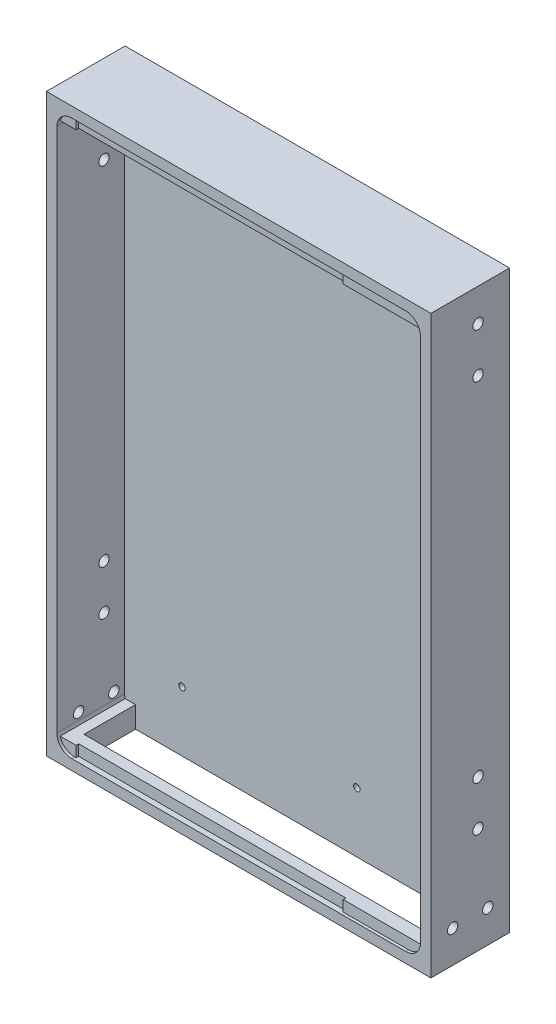
SolidWorks part; units mm, degrees
ref_plane "Front Plane" through (0, 0, 0) normal (0, 0, 1) x (1, 0, 0)
ref_plane "Top Plane" through (0, 0, 0) normal (0, 1, 0) x (1, 0, 0)
ref_plane "Right Plane" through (0, 0, 0) normal (1, 0, 0) x (0, 0, -1)
sketch "Sketch1" plane through (0, 0, 0) normal (0, 0, 1) x (1, 0, 0)
  line L1 (-88.5, -132.5) -> (88.5, -132.5)
  line L2 (-88.5, -132.5) -> (-88.5, 132.5)
  line L3 (-88.5, 132.5) -> (88.5, 132.5)
  line L4 (88.5, -132.5) -> (88.5, 132.5)
  line L5 (-88.5, -132.5) -> (88.5, 132.5) construction
  line L6 (-88.5, 132.5) -> (88.5, -132.5) construction
  circle A0 centre (-57.3, -104.9) radius 1.5 construction
  circle A1 centre (23.21, -104.9) radius 1.5 construction
  circle A2 centre (23.21, 104.9) radius 1.5 construction
  circle A3 centre (-57.3, 104.9) radius 1.5 construction
  circle A4 centre (-57.3, -104.9) radius 1.5
  circle A5 centre (23.21, -104.9) radius 1.5
  circle A6 centre (23.21, 104.9) radius 1.5
  circle A7 centre (-57.3, 104.9) radius 1.5
  point P0 (0, 0)
  dimension "D1" = 177
  dimension "D2" = 265
extrude "Boss-Extrude1" add sketch "Sketch1" along normal blind 5
sketch "Sketch2" plane through (0, 0, 5) normal (0, 0, 1) x (1, 0, 0)
  line L0 (83.7, -127.7) -> (83.7, 127.7)
  line L1 (83.7, 127.7) -> (-83.7, 127.7)
  line L2 (-83.7, 127.7) -> (-83.7, -127.7)
  line L3 (-83.7, -127.7) -> (83.7, -127.7)
  line L4 (88.5, -132.5) -> (88.5, 132.5)
  line L5 (88.5, 132.5) -> (-88.5, 132.5)
  line L6 (-88.5, 132.5) -> (-88.5, -132.5)
  line L7 (-88.5, -132.5) -> (88.5, -132.5)
  line L8 (88.5, -132.5) -> (88.5, 132.5)
  line L9 (88.5, 132.5) -> (-88.5, 132.5)
  line L10 (-88.5, 132.5) -> (-88.5, -132.5)
  line L11 (-88.5, -132.5) -> (88.5, -132.5)
  dimension "D1" = 0
  dimension "D2" = 4.8
extrude "Boss-Extrude2" add sketch "Sketch2" along normal blind 31.2
fillet "Fillet1" radius 6.82 4 edges at (83.7, 127.7, 20.6) (83.7, -127.7, 20.6) (-83.7, -127.7, 20.6) (-83.7, 127.7, 20.6)
sketch "Sketch4" plane through (0, 0, 5) normal (0, 0, 1) x (1, 0, 0)
  line L0 (-83.7, 122.7) -> (83.7, 122.7)
  line L1 (-83.7, -122.7) -> (83.7, -122.7)
  line L4 (83.7, -120.88) -> (83.7, 120.88)
  line L5 (76.88, 127.7) -> (-76.88, 127.7)
  line L6 (-83.7, 120.88) -> (-83.7, -120.88)
  line L7 (-76.88, -127.7) -> (76.88, -127.7)
  line L8 (83.7, -120.88) -> (83.7, 120.88)
  line L9 (76.88, 127.7) -> (-76.88, 127.7)
  line L10 (-83.7, 120.88) -> (-83.7, -120.88)
  line L11 (-76.88, -127.7) -> (76.88, -127.7)
  arc A4 (83.7, 120.88) -> (76.88, 127.7) centre (76.88, 120.88) ccw
  arc A5 (-76.88, 127.7) -> (-83.7, 120.88) centre (-76.88, 120.88) ccw
  arc A6 (-83.7, -120.88) -> (-76.88, -127.7) centre (-76.88, -120.88) ccw
  arc A7 (76.88, -127.7) -> (83.7, -120.88) centre (76.88, -120.88) ccw
  arc A8 (83.7, 120.88) -> (76.88, 127.7) centre (76.88, 120.88) ccw
  arc A9 (-76.88, 127.7) -> (-83.7, 120.88) centre (-76.88, 120.88) ccw
  arc A10 (-83.7, -120.88) -> (-76.88, -127.7) centre (-76.88, -120.88) ccw
  arc A11 (76.88, -127.7) -> (83.7, -120.88) centre (76.88, -120.88) ccw
  arc M12 (83.7, 120.88) -> (76.88, 127.7) centre (76.88, 120.88) ccw
  line M13 (76.88, 127.7) -> (-76.88, 127.7)
  arc M14 (-76.88, 127.7) -> (-83.7, 120.88) centre (-76.88, 120.88) ccw
  arc M16 (-83.7, -120.88) -> (-76.88, -127.7) centre (-76.88, -120.88) ccw
  line M17 (-76.88, -127.7) -> (76.88, -127.7)
  arc M18 (76.88, -127.7) -> (83.7, -120.88) centre (76.88, -120.88) ccw
  dimension "D2" = 5
  dimension "D3" = 5
  dimension "D1" = 0
extrude "Boss-Extrude3" add sketch "Sketch4" along normal offset from surface (29.9 mm away) 1.3 contours L1 M16 M17 M18 | L0 M14 M12 M13 region at (0, 125.1751, 5) region at (0, -125.1751, 5) up to face at (0, 0, 36.2)
sketch "Sketch5" plane through (0, 0, 34.9) normal (0, 0, 1) x (1, 0, 0)
  line L0 (83.4527, -122.7) -> (-83.4527, -122.7) construction
  line L1 (-76.88, -127.7) -> (76.88, -127.7) construction
  line L2 (76.88, 127.7) -> (-76.88, 127.7) construction
  line L3 (-83.4527, 122.7) -> (83.4527, 122.7) construction
  line L4 (83.4527, -122.7) -> (-83.4527, -122.7)
  line L5 (-76.88, -127.7) -> (76.88, -127.7)
  line L6 (76.88, 127.7) -> (-76.88, 127.7)
  line L7 (-83.4527, 122.7) -> (83.4527, 122.7)
  line L9 (-76.16, 127.7) -> (46.84, 127.7)
  line L10 (-76.16, 127.7) -> (-76.16, -127.7)
  line L11 (-76.16, -127.7) -> (46.84, -127.7)
  line L12 (46.84, 127.7) -> (46.84, -127.7)
  line L13 (-83.7, 120.88) -> (-83.7, -120.88) construction
  arc A0 (-83.4527, -122.7) -> (-76.88, -127.7) centre (-76.88, -120.88) ccw construction
  arc A1 (76.88, -127.7) -> (83.4527, -122.7) centre (76.88, -120.88) ccw construction
  arc A2 (-76.88, 127.7) -> (-83.4527, 122.7) centre (-76.88, 120.88) ccw construction
  arc A3 (83.4527, 122.7) -> (76.88, 127.7) centre (76.88, 120.88) ccw construction
  arc A4 (-83.4527, -122.7) -> (-76.88, -127.7) centre (-76.88, -120.88) ccw
  arc A5 (76.88, -127.7) -> (83.4527, -122.7) centre (76.88, -120.88) ccw
  arc A6 (-76.88, 127.7) -> (-83.4527, 122.7) centre (-76.88, 120.88) ccw
  arc A7 (83.4527, 122.7) -> (76.88, 127.7) centre (76.88, 120.88) ccw
  dimension "D1" = 7.54
  dimension "D2" = 123
extrude "Cut-Extrude1" cut sketch "Sketch5" against normal blind 1.2 contours L12 L4 L10 L5 | L12 L6 L10 L7 region at (-14.66, -125.2, 34.9) region at (-14.66, 125.2, 34.9)
sketch "Sketch9" plane through (0, -122.7, 0) normal (0, 1, 0) x (1, 0, 0)
  line L0 (-83.4527, -5) -> (83.4527, -5) construction
  line L1 (-78.7, -5) -> (78.7, -5)
  line L2 (-78.7, -5) -> (-78.7, -28.7)
  line L3 (-78.7, -28.7) -> (78.7, -28.7)
  line L4 (78.7, -5) -> (78.7, -28.7)
  line L5 (-83.7, -36.2) -> (-83.7, -5) construction
  line L6 (46.84, -33.7) -> (-76.16, -33.7) construction
  line L7 (83.7, -5) -> (83.7, -36.2) construction
  point P6 (-76.6388, -5)
  dimension "D1" = 5
  dimension "D2" = 5
  dimension "D3" = 5
extrude "Cut-Extrude3" cut sketch "Sketch9" against normal through all
sketch "Sketch10" plane through (88.5, 0, 0) normal (1, 0, 0) x (0, 0, -1)
  circle A0 centre (-10, -117.6) radius 2.4 construction
  circle A1 centre (-26.2, -117.6) radius 2.4 construction
  circle A2 centre (-10, -117.6) radius 2.4
  circle A3 centre (-26.2, -117.6) radius 2.4
extrude "Cut-Extrude4" cut sketch "Sketch10" against normal through all
sketch "Sketch11" plane through (0, 0, 0) normal (0, 0, -1) x (-1, 0, 0)
  line L0 (88.5, 132.5) -> (108.5, 132.5)
  line L1 (108.5, 132.5) -> (108.5, 82.5)
  line L2 (108.5, 82.5) -> (88.5, 82.5)
  line L3 (88.5, 132.5) -> (88.5, -132.5) construction
  line L4 (88.5, 82.5) -> (88.5, 132.5)
  line L9 (0, 132.5) -> (0, 0) construction
  line L10 (-88.5, 132.5) -> (88.5, 132.5) construction
  point P16 (100.2092, 132.5)
  point P17 (98.5, -40.3314)
  point P18 (98.5, -87.3257)
  dimension "D1" = 50
  dimension "D2" = 20
sketch "Sketch16" plane through (88.5, 0, 0) normal (1, 0, 0) x (0, 0, -1)
  line L0 (0, -132.5) -> (0, 132.5) construction
  line L1 (-36.2, 132.5) -> (0, 132.5) construction
  line L2 (-14.5, 117.5) -> (-14.5, 96.8453) construction
  line L3 (-14.5, 96.8453) -> (-14.5, -63.1547) construction
  line L4 (-14.5, -63.1547) -> (-14.5, -83.8094) construction
  line L8 (-36.2, 120.88) -> (-36.2, -120.88)
  line L9 (-36.2, -120.88) -> (-5, -120.88)
  line L10 (-5, -120.88) -> (-5, 120.88)
  line L11 (-5, 120.88) -> (-36.2, 120.88)
  line L16 (-36.2, 120.88) -> (-36.2, -120.88) construction
  line L17 (-36.2, -120.88) -> (-5, -120.88) construction
  line L18 (-5, -120.88) -> (-5, 120.88) construction
  line L19 (-5, 120.88) -> (-36.2, 120.88) construction
  circle A1 centre (-14.5, 117.5) radius 2.4
  circle A2 centre (-14.5, 96.8453) radius 2.4
  circle A3 centre (-14.5, -63.1547) radius 2.4
  circle A4 centre (-14.5, -83.8094) radius 2.4
  point P16 (-14.5, -78.7358)
  dimension "D3" = 4.8
  dimension "D2" = 14.5
  dimension "D4" = 15
  dimension "D5" = 20.6547
  dimension "D6" = 160
  dimension "D1" = 0
extrude "Cut-Extrude7" cut sketch "Sketch16" against normal up to surface (177 mm away) up to face at (-88.5, -117.6, 7.6)
